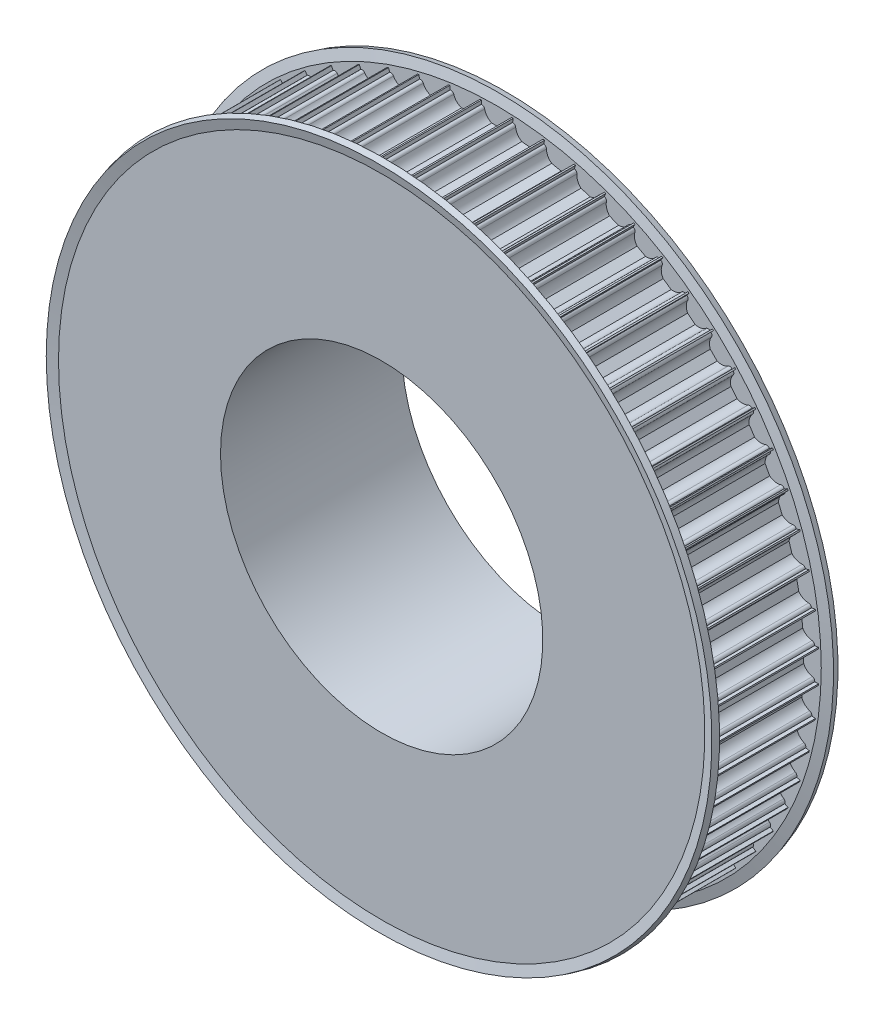
SolidWorks part; units mm, degrees
ref_plane "Front Plane" through (0, 0, 0) normal (0, 0, 1) x (1, 0, 0)
ref_plane "Top Plane" through (0, 0, 0) normal (0, 1, 0) x (1, 0, 0)
ref_plane "Right Plane" through (0, 0, 0) normal (1, 0, 0) x (0, 0, -1)
ref_axis "Axis1" through (0, 0, -88.99) along (0, 0, 1)
sketch "Sketch1" plane through (0, 0, 0) normal (1, 0, 0) x (0, 0, -1)
  line L0 (0, 40) -> (0, 80)
  line L1 (0, 80) -> (30, 80)
  line L2 (30, 80) -> (30, 55.5)
  line L3 (30, 55.5) -> (45, 55.5)
  line L4 (45, 55.5) -> (45, 40)
  line L5 (45, 40) -> (0, 40)
  dimension "D1" = 40
  dimension "D2" = 40
  dimension "D3" = 30
  dimension "D4" = 15
  dimension "D5" = 15.5
revolve "Revolve1" add sketch "Sketch1" angle 360 about axis through (0, 0, -88.99) along (0, 0, 1)
sketch "Sketch2" plane through (0, 0, 0) normal (0, 0, 1) x (1, 0, 0)
  line L0 (3.6742, 79) -> (3.75, 79)
  line L1 (-3.75, 81) -> (3.75, 81)
  line L2 (-3.75, 81) -> (-3.75, 79)
  line L3 (-3.75, 79) -> (-3.6742, 79)
  line L4 (3.75, 81) -> (3.75, 79)
  line L5 (-1.199, 76.25) -> (1.199, 76.25)
  arc A0 (-2.9394, 78.4) -> (-1.199, 76.25) centre (0, 79) ccw
  arc A1 (-2.9394, 78.4) -> (-3.6742, 79) centre (-3.6742, 78.25) ccw
  arc A2 (2.9394, 78.4) -> (3.6742, 79) centre (3.6742, 78.25) cw
  arc A3 (1.199, 76.25) -> (2.9394, 78.4) centre (0, 79) ccw
  dimension "D1" = 3
  dimension "D5" = 0.75
  dimension "D6" = 0.75
  dimension "D2" = 2
  dimension "D3" = 7.5
  dimension "D4" = 79
  dimension "D7" = 2.75
extrude "Cut-Extrude1" cut sketch "Sketch2" against normal through all
pattern_circular "CirPattern1" count 64 over 360 about axis through (0, 0, -88.99) along (0, 0, 1) of "Cut-Extrude1"
sketch "Sketch3" plane through (0, 0, 0) normal (1, 0, 0) x (0, 0, -1)
  line L0 (0, 79.9121) -> (30, 79.9121) construction
  line L1 (0, 80.6121) -> (1.5, 80.6121) construction
  line L2 (0, 80.6121) -> (0, 75.6121)
  line L3 (0, 75.6121) -> (1.5, 75.6121)
  line L4 (1.5, 80.6121) -> (1.5, 75.6121)
  line L5 (1.5, 80.6121) -> (0, 80.2101) construction
  line L6 (1.5, 80.6121) -> (0.8569, 83.0121)
  line L7 (0, 80.2101) -> (-0.6431, 82.6101)
  line L8 (0.8569, 83.0121) -> (-0.6431, 82.6101)
  line L9 (15, -40.9775) -> (15, -38.6245) construction
  line L10 (30, -40.9775) -> (0, -40.9775) construction
  line L11 (0, -32.718) -> (0, -33.6265) construction
  line L12 (28.5, 80.6121) -> (30, 80.2101) construction
  line L13 (30, 80.6121) -> (28.5, 80.6121) construction
  line L14 (29.1431, 83.0121) -> (30.6431, 82.6101)
  line L15 (30, 80.2101) -> (30.6431, 82.6101)
  line L16 (28.5, 80.6121) -> (29.1431, 83.0121)
  line L17 (28.5, 80.6121) -> (28.5, 75.6121)
  line L18 (30, 75.6121) -> (28.5, 75.6121)
  line L19 (30, 80.6121) -> (30, 75.6121)
  dimension "D1" = 1.5
  dimension "D2" = 5
  dimension "D3" = 1.5
  dimension "D4" = 165
  dimension "D5" = 2.4
  dimension "D6" = 0.7
revolve "Revolve2" add sketch "Sketch3" angle 360 about axis through (0, 0, -88.99) along (0, 0, 1) region at (0, 79.2686, -0.6446) region at (0, 79.2686, -29.3554)
